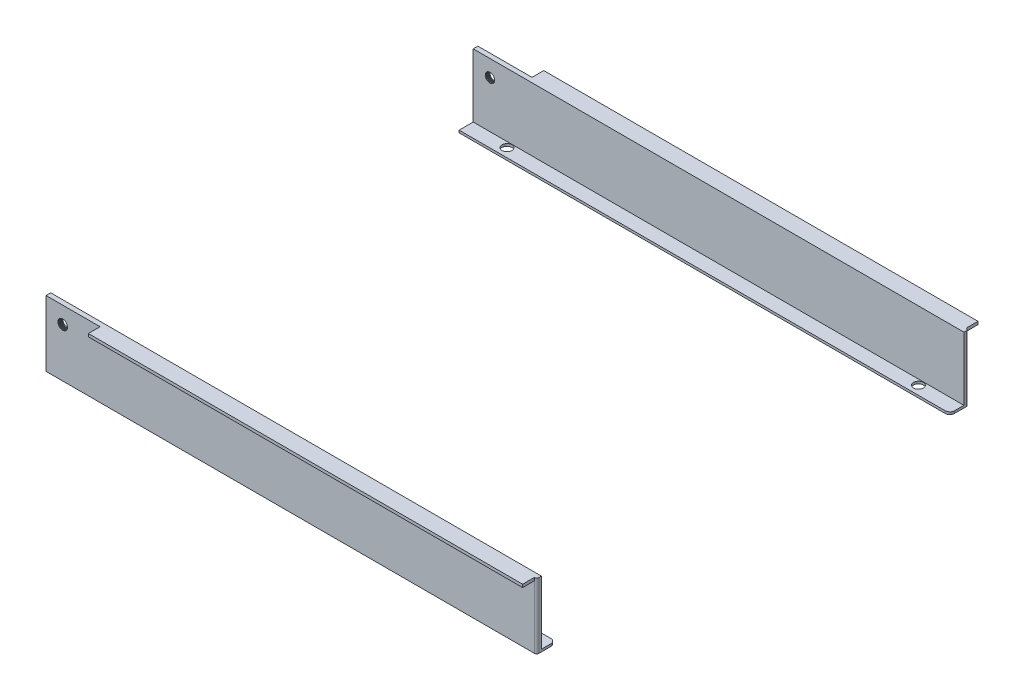
SolidWorks part; units mm, degrees
ref_plane "前基準面" through (0, 0, 0) normal (0, 0, 1) x (1, 0, 0)
ref_plane "上基準面" through (0, 0, 0) normal (0, 1, 0) x (1, 0, 0)
ref_plane "右基準面" through (0, 0, 0) normal (1, 0, 0) x (0, 0, -1)
sketch "草圖1" plane through (0, 0, 0) normal (0, 0, 1) x (1, 0, 0)
  line L1 (-115, 15) -> (115, 15)
  line L2 (-115, 15) -> (-115, -15)
  line L3 (-115, -15) -> (115, -15)
  line L4 (115, 15) -> (115, -15)
  line L5 (0, -15) -> (0, 15) construction
  line L6 (-115, 0) -> (115, 0) construction
  point P0 (0, 0)
  dimension "D1" = 30
  dimension "D2" = 230
extrude "填料-伸長1" add sketch "草圖1" along normal blind 2
sketch "草圖2" plane through (0, 0, 2) normal (0, 0, 1) x (1, 0, 0)
  line L1 (115, 15) -> (-115, 15) construction
  line L2 (115, -15) -> (115, 15) construction
  line L3 (-68, 15) -> (115, 15)
  line L4 (-68, 15) -> (-68, 14)
  line L5 (-68, 14) -> (115, 14)
  line L6 (115, 15) -> (115, 14)
extrude "填料-伸長2" add sketch "草圖2" along normal blind 5
fillet "圓角1" radius 2 1 edges at (-68, 14.5, 7)
fillet "圓角2" radius 2 1 edges at (115, 14.5, 7)
sketch "草圖3" plane through (0, 0, 0) normal (0, 0, -1) x (-1, 0, 0)
  line L0 (115, 15) -> (115, -15) construction
  line L1 (-115, -15) -> (115, -15)
  line L2 (-115, -15) -> (-115, -14.0001)
  line L3 (-115, -14.0001) -> (115, -14.0001)
  line L4 (115, -15) -> (115, -14.0001)
extrude "填料-伸長3" add sketch "草圖3" along normal blind 6
fillet "圓角3" radius 2 1 edges at (-115, -14.5001, -6)
fillet "圓角4" radius 2 1 edges at (115, -14.5001, -6)
sketch "草圖4" plane through (0, 0, 2) normal (0, 0, 1) x (1, 0, 0)
  circle A0 centre (-86.9057, 5.9156) radius 2
extrude "除料-伸長1" cut sketch "草圖4" against normal blind 6
thread "螺紋1" pitch 0.3175 method cut profile "螺紋輪廓1" start angle 0, offset 0, length 10, pitch 0.5, diameter 4
ref_plane "平面1" through (-84.9057, 5.9156, 0) normal (0, -1, 0) x (1, 0, 0)
sketch "螺紋輪廓1" plane through (-84.9057, 5.9156, 0) normal (0, -1, 0) x (1, 0, 0)
  line L0 (0, 0) -> (0, 0.3175) construction
  line L1 (0, 0) -> (0.2, 0.1155)
  line L2 (0.2, 0.1155) -> (0.2, 0.1552)
  line L3 (0.2, 0.1552) -> (0, 0.2706)
  line L4 (0.2, 0.1353) -> (0, 0.1353) construction
  line L11 (0, 0) -> (0, 0.2706)
  point P2 (0, 0)
  dimension "Pitch" = 0.3175
  dimension "Profile_Angle" = 60
  dimension "Profile_Land" = 0.0397
  dimension "Profile_Height" = 0.2
fillet "圓角5" radius 2 1 edges at (-115, 15, 1)
fillet "圓角6" radius 1 3 edges at (1, 15, 0) (-114.4142, 14.4142, 0) (-115, -0.5001, 0)
fillet "圓角7" radius 1 1 edges at (115, -0.5, 2)
sketch "草圖6" plane through (0, 0, 7) normal (0, 0, 1) x (1, 0, 0)
  line L1 (-118.3014, 16.7729) -> (-94.0415, 16.7729)
  line L2 (-118.3014, 16.7729) -> (-118.3014, -19.6953)
  line L3 (-118.3014, -19.6953) -> (-94.0415, -19.6953)
  line L4 (-94.0415, 16.7729) -> (-94.0415, -19.6953)
extrude "除料-伸長5" cut sketch "草圖6" against normal blind 15
sketch "草圖7" plane through (0, -15, 0) normal (0, -1, 0) x (1, 0, 0)
  circle A0 centre (-77.3987, -2.2601) radius 2.1
  circle A1 centre (97.9009, -2.2601) radius 2.1
extrude "除料-伸長6" cut sketch "草圖7" against normal blind 10
sketch "草圖8" plane through (115, 0, 0) normal (1, 0, 0) x (0, 0, -1)
  line L0 (0, -14.0001) -> (0, 14) construction
  line L1 (-7, 15) -> (0, 15)
  line L2 (-7, 15) -> (-7, 13)
  line L3 (-7, 13) -> (0, 13)
  line L4 (0, 15) -> (0, 13)
extrude "除料-伸長8" cut sketch "草圖8" against normal blind 218
sketch "草圖9" plane through (0, 0, 2) normal (0, 0, 1) x (1, 0, 0)
  line L1 (114, 13) -> (-71, 13)
  line L2 (114, 13) -> (114, 11.76)
  line L3 (114, 11.76) -> (-71, 11.76)
  line L4 (-71, 13) -> (-71, 11.76)
extrude "填料-伸長4" add sketch "草圖9" along normal blind 5
ref_plane "平面2" through (0, 0, -90) normal (0, 0, -1) x (-1, 0, 0)
mirror "鏡射3" about plane through (0, 0, -90) normal (0, 0, -1) of bodies 113
